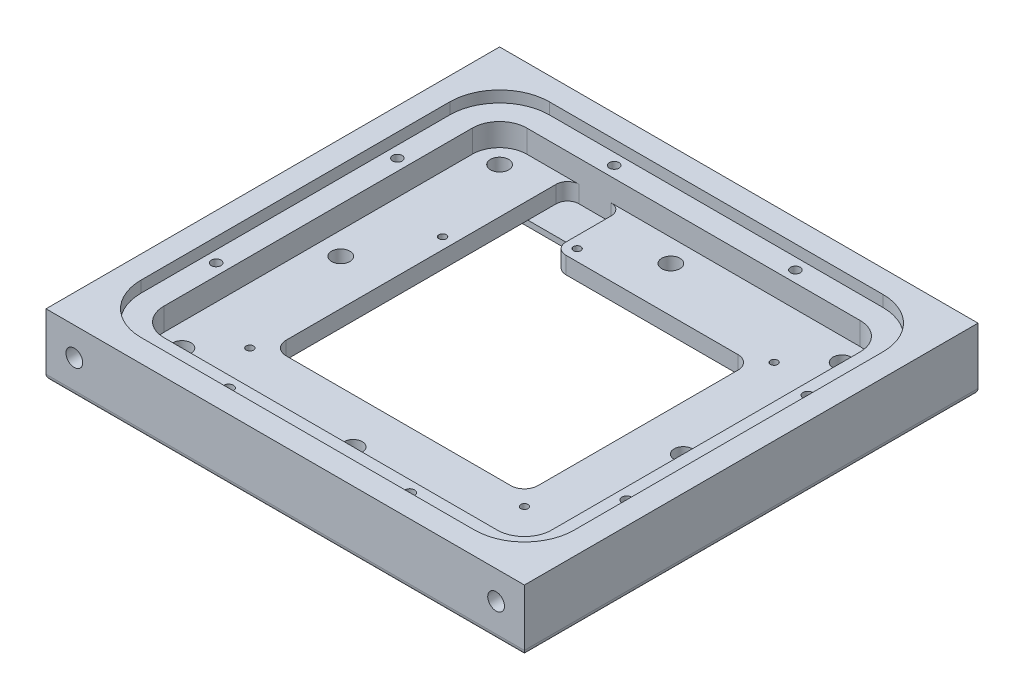
SolidWorks part; units mm, degrees
material "PE High Density"
ref_plane "Front Plane" through (0, 0, 0) normal (0, 0, 1) x (1, 0, 0)
ref_plane "Top Plane" through (0, 0, 0) normal (0, 1, 0) x (1, 0, 0)
ref_plane "Right Plane" through (0, 0, 0) normal (1, 0, 0) x (0, 0, -1)
sketch "Sketch2" plane through (0, 0, 0) normal (0, 1, 0) x (1, 0, 0)
  line L0 (-41.656, 22.1996) -> (-19.9136, 22.1996)
  line L1 (41.656, -38.1762) -> (-41.656, -38.1762)
  line L2 (41.656, -38.1762) -> (41.656, 38.1762)
  line L3 (41.656, 38.1762) -> (-41.656, 38.1762)
  line L4 (-41.656, -38.1762) -> (-41.656, 38.1762)
  line L5 (41.656, -38.1762) -> (-41.656, 38.1762) construction
  line L6 (41.656, 38.1762) -> (-41.656, -38.1762) construction
  line L7 (-19.9136, 22.1996) -> (-19.9136, 38.1762)
  line L8 (67.056, -63.5762) -> (-67.056, -63.5762)
  line L9 (-67.056, -63.5762) -> (-67.056, 63.5762)
  line L10 (67.056, 63.5762) -> (-67.056, 63.5762)
  line L11 (67.056, -63.5762) -> (67.056, 63.5762)
  point P0 (0, 0)
  point P13 (-38.481, -35.0012)
  point P14 (38.481, -35.0012)
  point P15 (38.481, 35.0012)
  point P16 (-16.7386, 35.0012)
  point P17 (-38.481, 19.0246)
  dimension "D1" = 83.312
  dimension "D2" = 76.3524
  dimension "D3" = 21.7424
  dimension "D4" = 15.9766
  dimension "D6" = 3.175
  dimension "D7" = 3.175
  dimension "D8" = 57.2008
  dimension "D9" = 80.137
  dimension "D10" = 24.9174
  dimension "D11" = 73.1774
  dimension "D5" = 25.4
extrude "Boss-Extrude1" add sketch "Sketch2" along normal blind 15.875 contours L8 L11 L10 L9 L1 L4 L3 L2 | L0 L7 L3 L4 region at (-30.7848, 0, -30.1879) region at (0, 0, 61.7281)
sketch "Sketch4" plane through (0, 0, 0) normal (0, 1, 0) x (1, 0, 0)
  line L0 (41.656, -38.1762) -> (41.656, 38.1762) construction
  line L1 (41.656, 38.1762) -> (-19.9136, 38.1762) construction
  line L2 (41.656, -38.1762) -> (-41.656, -38.1762) construction
  line L3 (-41.656, -38.1762) -> (-41.656, 22.1996) construction
  line L4 (-41.656, 22.1996) -> (-19.9136, 22.1996) construction
  line L5 (41.656, -38.1762) -> (41.656, 38.1762)
  line L6 (41.656, 38.1762) -> (-19.9136, 38.1762)
  line L7 (41.656, -38.1762) -> (-41.656, -38.1762)
  line L8 (-41.656, -38.1762) -> (-41.656, 22.1996)
  line L9 (-41.656, 22.1996) -> (-19.9136, 22.1996)
  line L10 (-19.9136, 22.1996) -> (-19.9136, 38.1762) construction
  line L11 (-19.9136, 22.1996) -> (-19.9136, 38.1762)
  line L12 (35.306, 31.8262) -> (-13.5636, 31.8262)
  line L13 (-13.5636, 15.8496) -> (-13.5636, 31.8262)
  line L14 (-35.306, 15.8496) -> (-13.5636, 15.8496)
  line L15 (-35.306, -31.8262) -> (-35.306, 15.8496)
  line L16 (35.306, -31.8262) -> (-35.306, -31.8262)
  line L17 (35.306, -31.8262) -> (35.306, 31.8262)
  dimension "D1" = 6.35
extrude "Boss-Extrude2" add sketch "Sketch4" along normal blind 9.525
sketch "Sketch5" plane through (0, 0, 0) normal (0, -1, 0) x (1, 0, 0)
  line L5 (46.736, -50.8762) -> (-46.736, -50.8762)
  line L6 (54.356, -43.2562) -> (54.356, 43.2562)
  line L7 (46.736, 50.8762) -> (-46.736, 50.8762)
  line L8 (-54.356, -43.2562) -> (-54.356, 43.2562)
  line L9 (54.356, -50.8762) -> (-54.356, 50.8762) construction
  line L10 (54.356, 50.8762) -> (-54.356, -50.8762) construction
  arc A0 (46.736, -50.8762) -> (54.356, -43.2562) centre (46.736, -43.2562) ccw
  arc A1 (-46.736, -50.8762) -> (-54.356, -43.2562) centre (-46.736, -43.2562) cw
  arc A2 (54.356, 43.2562) -> (46.736, 50.8762) centre (46.736, 43.2562) ccw
  arc A3 (-46.736, 50.8762) -> (-54.356, 43.2562) centre (-46.736, 43.2562) ccw
  point P0 (0, 0)
  dimension "D3" = 7.62
  dimension "D1" = 108.712
  dimension "D2" = 101.7524
extrude "Cut-Extrude2" cut sketch "Sketch5" against normal blind 3.175
hole_wizard "M2.5x0.45 Tapped Hole1" positions "Sketch6" profile "Sketch7" tap size "M2.5x0.45" standard "ANSI Metric"
sketch "Sketch6" plane through (0, 3.175, 0) normal (0, -1, 0) x (-1, 0, 0)
  point P0 (38.481, -35.0012)
  point P3 (-38.481, -35.0012)
  point P6 (38.481, 19.0246)
  point P9 (16.7386, 35.0012)
  point P12 (-38.481, 35.0012)
sketch "Sketch7" plane through (-38.481, 3.175, 35.0012) normal (1, 0, 0) x (0, 0, -1)
  line L0 (0, 0) -> (0, 6.9659)
  line L1 (0, 6.9659) -> (1.025, 6.35)
  line L2 (1.025, 6.35) -> (1.025, 0)
  line L5 (1.025, 0) -> (0, 0)
  line L10 (0, 6.9659) -> (-1.025, 6.35) construction
  line L11 (0, -6.35) -> (0, 107.95) construction
  dimension "Tap Drill Dia." = 2.05
  dimension "Tap Drill Depth" = 6.35
  dimension "Drill Angle" = 118
cosmetic thread "Hole Thread1" parameters "D1"=5.08, "D2"=2.5
cosmetic thread "Hole Thread2" parameters "D1"=5.08, "D2"=2.5
cosmetic thread "Hole Thread3" parameters "D1"=5.08, "D2"=2.5
cosmetic thread "Hole Thread4" parameters "D1"=5.08, "D2"=2.5
cosmetic thread "Hole Thread5" parameters "D1"=5.08, "D2"=2.5
hole_wizard "#10 Clearance Hole1" positions "Sketch8" profile "Sketch9" hole size "#10" standard "ANSI Inch" end condition through all
sketch "Sketch8" plane through (0, 3.175, 0) normal (0, -1, 0) x (-1, 0, 0)
  line L0 (54.356, -43.2562) -> (54.356, 43.2562) construction
  line L1 (-46.736, -50.8762) -> (46.736, -50.8762) construction
  line L2 (46.736, 50.8762) -> (-46.736, 50.8762) construction
  line L3 (-54.356, 43.2562) -> (-54.356, -43.2562) construction
  point P0 (48.006, -44.5262)
  point P2 (0, -44.5262)
  point P4 (-48.006, -44.5262)
  point P6 (-48.006, 0)
  point P8 (-48.006, 44.5262)
  point P10 (0, 44.5262)
  point P12 (48.006, 44.5262)
  point P14 (48.006, 0)
  dimension "D1" = 6.35
  dimension "D2" = 6.35
  dimension "D3" = 6.35
  dimension "D4" = 6.35
sketch "Sketch9" plane through (-48.006, 3.175, 44.5262) normal (1, 0, 0) x (0, 0, -1)
  line L0 (0, 0) -> (0, 12.7)
  line L1 (0, 12.7) -> (2.5527, 12.7)
  line L2 (2.5527, 12.7) -> (2.5527, 0)
  line L5 (2.5527, 0) -> (0, 0)
  line L11 (0, -6.35) -> (0, 107.95) construction
  dimension "Thru Hole Dia." = 5.1054
  dimension "Thru Hole Depth" = 12.7
sketch "Sketch10" plane through (0, 15.875, 0) normal (0, 1, 0) x (1, 0, 0)
  line L4 (54.356, -43.2562) -> (54.356, 43.2562)
  line L5 (-46.736, -50.8762) -> (46.736, -50.8762)
  line L6 (-54.356, 43.2562) -> (-54.356, -43.2562)
  line L7 (46.736, 50.8762) -> (-46.736, 50.8762)
  line L8 (54.356, -43.2562) -> (54.356, 43.2562)
  line L9 (-46.736, -50.8762) -> (46.736, -50.8762)
  line L10 (-54.356, 43.2562) -> (-54.356, -43.2562)
  line L11 (46.736, 50.8762) -> (-46.736, 50.8762)
  arc A4 (54.356, 43.2562) -> (46.736, 50.8762) centre (46.736, 43.2562) ccw
  arc A5 (46.736, -50.8762) -> (54.356, -43.2562) centre (46.736, -43.2562) ccw
  arc A6 (-54.356, -43.2562) -> (-46.736, -50.8762) centre (-46.736, -43.2562) ccw
  arc A7 (-46.736, 50.8762) -> (-54.356, 43.2562) centre (-46.736, 43.2562) ccw
  arc A8 (54.356, 43.2562) -> (46.736, 50.8762) centre (46.736, 43.2562) ccw
  arc A9 (46.736, -50.8762) -> (54.356, -43.2562) centre (46.736, -43.2562) ccw
  arc A10 (-54.356, -43.2562) -> (-46.736, -50.8762) centre (-46.736, -43.2562) ccw
  arc A11 (-46.736, 50.8762) -> (-54.356, 43.2562) centre (-46.736, 43.2562) ccw
  dimension "D1" = 0
extrude "Cut-Extrude3" cut sketch "Sketch10" against normal up to surface (6.35 mm away) up to face at (-38.481, 9.525, 33.9762)
sketch "Sketch11" plane through (0, 3.175, 0) normal (0, -1, 0) x (1, 0, 0)
  line L8 (43.2435, 39.7637) -> (-43.2435, 39.7637)
  line L9 (-43.2435, 39.7637) -> (-43.2435, -39.7637)
  line L10 (-43.2435, -39.7637) -> (43.2435, -39.7637)
  line L11 (43.2435, -39.7637) -> (43.2435, 39.7637)
  line L12 (40.0685, 39.7637) -> (-40.0685, 39.7637)
  line L13 (-43.2435, 36.5887) -> (-43.2435, -36.5887)
  line L14 (-40.0685, -39.7637) -> (40.0685, -39.7637)
  line L15 (43.2435, -36.5887) -> (43.2435, 36.5887)
  arc A0 (40.0685, -39.7637) -> (43.2435, -36.5887) centre (40.0685, -36.5887) ccw
  arc A1 (-43.2435, -36.5887) -> (-40.0685, -39.7637) centre (-40.0685, -36.5887) ccw
  arc A2 (40.0685, 39.7637) -> (43.2435, 36.5887) centre (40.0685, 36.5887) cw
  arc A3 (-40.0685, 39.7637) -> (-43.2435, 36.5887) centre (-40.0685, 36.5887) ccw
  dimension "D2" = 3.175
  dimension "D1" = 1.5875
extrude "Cut-Extrude4" cut sketch "Sketch11" against normal blind 1.6
sketch "Sketch12" plane through (0, 4.775, 0) normal (0, -1, 0) x (1, 0, 0)
  line L0 (-35.306, 31.8262) -> (-35.306, -15.8496) construction
  line L1 (35.306, 31.8262) -> (-35.306, 31.8262)
  line L2 (35.306, 31.8262) -> (35.306, -31.8262)
  line L3 (35.306, -31.8262) -> (-35.306, -31.8262)
  line L4 (-35.306, 31.8262) -> (-35.306, -31.8262)
  line L5 (-13.5636, -31.8262) -> (35.306, -31.8262) construction
extrude "Cut-Extrude5" cut sketch "Sketch12" against normal through all
fillet "Fillet1" radius 3.81 4 edges at (35.306, 7.15, -31.8262) (-35.306, 7.15, -31.8262) (35.306, 7.15, 31.8262) (-35.306, 7.15, 31.8262)
sketch "Sketch13" plane through (0, 0, 0) normal (0, -1, 0) x (1, 0, 0)
  line L4 (54.356, -43.2562) -> (54.356, 43.2562)
  line L5 (46.736, 50.8762) -> (-46.736, 50.8762)
  line L6 (-54.356, 43.2562) -> (-54.356, -43.2562)
  line L7 (-46.736, -50.8762) -> (46.736, -50.8762)
  line L8 (54.356, -43.2562) -> (54.356, 43.2562)
  line L9 (46.736, 50.8762) -> (-46.736, 50.8762)
  line L10 (-54.356, 43.2562) -> (-54.356, -43.2562)
  line L11 (-46.736, -50.8762) -> (46.736, -50.8762)
  line L12 (67.056, 63.5762) -> (-67.056, 63.5762)
  line L13 (-67.056, 63.5762) -> (-67.056, -63.5762)
  line L14 (-67.056, -63.5762) -> (67.056, -63.5762)
  line L15 (67.056, -63.5762) -> (67.056, 63.5762)
  line L16 (67.056, 63.5762) -> (-67.056, 63.5762)
  line L17 (-67.056, 63.5762) -> (-67.056, -63.5762)
  line L18 (-67.056, -63.5762) -> (67.056, -63.5762)
  line L19 (67.056, -63.5762) -> (67.056, 63.5762)
  arc A4 (46.736, -50.8762) -> (54.356, -43.2562) centre (46.736, -43.2562) ccw
  arc A5 (54.356, 43.2562) -> (46.736, 50.8762) centre (46.736, 43.2562) ccw
  arc A6 (-46.736, 50.8762) -> (-54.356, 43.2562) centre (-46.736, 43.2562) ccw
  arc A7 (-54.356, -43.2562) -> (-46.736, -50.8762) centre (-46.736, -43.2562) ccw
  arc A8 (46.736, -50.8762) -> (54.356, -43.2562) centre (46.736, -43.2562) ccw
  arc A9 (54.356, 43.2562) -> (46.736, 50.8762) centre (46.736, 43.2562) ccw
  arc A10 (-46.736, 50.8762) -> (-54.356, 43.2562) centre (-46.736, 43.2562) ccw
  arc A11 (-54.356, -43.2562) -> (-46.736, -50.8762) centre (-46.736, -43.2562) ccw
  dimension "D1" = 0
  dimension "D2" = 0
extrude "Cut-Extrude6" cut sketch "Sketch13" against normal blind 1.5875
fillet "Fillet2" radius 1.5875 4 edges at (67.056, 1.5875, 0) (0, 1.5875, 63.5762) (-67.056, 1.5875, 0) (0, 1.5875, -63.5762)
sketch "Sketch14" plane through (0, 9.525, 0) normal (0, 1, 0) x (1, 0, 0)
  line L1 (-35.306, 28.0162) -> (-19.9136, 28.0162)
  line L2 (-35.306, 28.0162) -> (-35.306, 50.8762)
  line L3 (-35.306, 50.8762) -> (-19.9136, 50.8762)
  line L4 (-19.9136, 28.0162) -> (-19.9136, 50.8762)
  line L6 (46.736, 50.8762) -> (-46.736, 50.8762) construction
  circle A0 centre (-16.7386, 35.0012) radius 1.025 construction
  dimension "D1" = 3.175
extrude "Cut-Extrude7" cut sketch "Sketch14" against normal up to surface (4.75 mm away) up to face at (0, 4.775, 0)
fillet "Fillet3" radius 3.175 3 edges at (-19.9136, 7.15, -50.8762) (-35.306, 7.15, -50.8762) (-19.9136, 7.15, -31.8262)
sketch "Sketch15" plane through (0, 15.875, 0) normal (0, 1, 0) x (1, 0, 0)
  line L0 (54.356, -43.2562) -> (54.356, 43.2562) construction
  line L1 (-46.736, -50.8762) -> (46.736, -50.8762) construction
  line L2 (-54.356, 43.2562) -> (-54.356, -43.2562) construction
  line L3 (46.736, 50.8762) -> (-46.736, 50.8762) construction
  line L4 (54.356, -43.2562) -> (54.356, 43.2562)
  line L5 (-46.736, -50.8762) -> (46.736, -50.8762)
  line L6 (-54.356, 43.2562) -> (-54.356, -43.2562)
  line L7 (46.736, 50.8762) -> (-46.736, 50.8762)
  line L8 (60.706, -43.2562) -> (60.706, 43.2562)
  line L9 (46.736, 57.2262) -> (-46.736, 57.2262)
  line L10 (-60.706, 43.2562) -> (-60.706, -43.2562)
  line L11 (-46.736, -57.2262) -> (46.736, -57.2262)
  line L16 (-67.056, -63.5762) -> (67.056, -63.5762)
  line L17 (67.056, -63.5762) -> (67.056, 63.5762)
  line L18 (67.056, 63.5762) -> (-67.056, 63.5762)
  line L19 (-67.056, 63.5762) -> (-67.056, -63.5762)
  line L20 (-67.056, -63.5762) -> (67.056, -63.5762)
  line L21 (67.056, -63.5762) -> (67.056, 63.5762)
  line L22 (67.056, 63.5762) -> (-67.056, 63.5762)
  line L23 (-67.056, 63.5762) -> (-67.056, -63.5762)
  arc A0 (46.736, -50.8762) -> (54.356, -43.2562) centre (46.736, -43.2562) ccw construction
  arc A1 (-54.356, -43.2562) -> (-46.736, -50.8762) centre (-46.736, -43.2562) ccw construction
  arc A2 (54.356, 43.2562) -> (46.736, 50.8762) centre (46.736, 43.2562) ccw construction
  arc A3 (-46.736, 50.8762) -> (-54.356, 43.2562) centre (-46.736, 43.2562) ccw construction
  arc A4 (46.736, -50.8762) -> (54.356, -43.2562) centre (46.736, -43.2562) ccw
  arc A5 (-54.356, -43.2562) -> (-46.736, -50.8762) centre (-46.736, -43.2562) ccw
  arc A6 (54.356, 43.2562) -> (46.736, 50.8762) centre (46.736, 43.2562) ccw
  arc A7 (-46.736, 50.8762) -> (-54.356, 43.2562) centre (-46.736, 43.2562) ccw
  arc A8 (60.706, 43.2562) -> (46.736, 57.2262) centre (46.736, 43.2562) ccw
  arc A9 (-46.736, 57.2262) -> (-60.706, 43.2562) centre (-46.736, 43.2562) ccw
  arc A10 (-60.706, -43.2562) -> (-46.736, -57.2262) centre (-46.736, -43.2562) ccw
  arc A11 (46.736, -57.2262) -> (60.706, -43.2562) centre (46.736, -43.2562) ccw
  line M29 (-67.056, -63.5762) -> (67.056, -63.5762)
  line M30 (67.056, -63.5762) -> (67.056, 63.5762)
  line M31 (67.056, 63.5762) -> (-67.056, 63.5762)
  line M32 (-67.056, 63.5762) -> (-67.056, -63.5762)
  dimension "D1" = 6.35
  dimension "D2" = 0
extrude "Boss-Extrude3" add sketch "Sketch15" along normal blind 3.175 contours A11 L11 A10 L10 A9 L9 A8 L8 M32 M29 M30 M31 region at (-65.2079, 15.875, 0)
hole_wizard "#6-32 Tapped Hole1" positions "Sketch16" profile "Sketch18" tap size "#6-32" standard "ANSI Inch"
sketch "Sketch16" plane through (0, 15.875, 0) normal (0, 1, 0) x (1, 0, 0)
  line L28 (57.531, -43.2562) -> (57.531, 43.2562)
  line L29 (-46.736, -54.0512) -> (46.736, -54.0512)
  line L30 (-57.531, 43.2562) -> (-57.531, -43.2562)
  line L31 (46.736, 54.0512) -> (-46.736, 54.0512)
  line L32 (57.531, -43.2562) -> (57.531, 43.2562) construction
  line L33 (-46.736, -54.0512) -> (46.736, -54.0512) construction
  line L34 (-57.531, 43.2562) -> (-57.531, -43.2562) construction
  line L35 (46.736, 54.0512) -> (-46.736, 54.0512) construction
  arc A24 (57.531, 43.2562) -> (46.736, 54.0512) centre (46.736, 43.2562) ccw
  arc A25 (46.736, -54.0512) -> (57.531, -43.2562) centre (46.736, -43.2562) ccw
  arc A26 (-57.531, -43.2562) -> (-46.736, -54.0512) centre (-46.736, -43.2562) ccw
  arc A27 (-46.736, 54.0512) -> (-57.531, 43.2562) centre (-46.736, 43.2562) ccw
  arc A28 (57.531, 43.2562) -> (46.736, 54.0512) centre (46.736, 43.2562) ccw construction
  arc A29 (46.736, -54.0512) -> (57.531, -43.2562) centre (46.736, -43.2562) ccw construction
  arc A30 (-57.531, -43.2562) -> (-46.736, -54.0512) centre (-46.736, -43.2562) ccw construction
  arc A31 (-46.736, 54.0512) -> (-57.531, 43.2562) centre (-46.736, 43.2562) ccw construction
  point P141 (-25.4, 54.0512)
  point P143 (-57.531, 25.4)
  point P145 (-57.531, -25.4)
  point P147 (-25.4, -54.0512)
  dimension "D2" = 25.4
  dimension "D3" = 25.4
  dimension "D4" = 25.4
  dimension "D1" = 3.175
cosmetic thread "Hole Thread6" parameters "D1"=14.224, "D2"=3.5052
cosmetic thread "Hole Thread7" parameters "D1"=14.224, "D2"=3.5052
cosmetic thread "Hole Thread8" parameters "D1"=14.224, "D2"=3.5052
cosmetic thread "Hole Thread9" parameters "D1"=14.224, "D2"=3.5052
sketch "Sketch18" plane through (-25.4, 15.875, 54.0512) normal (1, 0, 0) x (0, 0, 1)
  line L0 (0, 0) -> (0, 10.3377)
  line L1 (0, 10.3377) -> (1.3525, 9.525)
  line L2 (1.3525, 9.525) -> (1.3525, 0)
  line L5 (1.3525, 0) -> (0, 0)
  line L10 (0, 10.3377) -> (-1.3526, 9.525) construction
  line L11 (0, -6.35) -> (0, 107.95) construction
  dimension "Tap Drill Dia." = 2.7051
  dimension "Tap Drill Depth" = 9.525
  dimension "Drill Angle" = 118
mirror "Mirror1" about plane through (0, 0, 0) normal (1, 0, 0) of "#6-32 Tapped Hole1"
cosmetic thread "Hole Thread10" parameters "D1"=14.224, "D2"=3.5052
cosmetic thread "Hole Thread11" parameters "D1"=14.224, "D2"=3.5052
cosmetic thread "Hole Thread12" parameters "D1"=14.224, "D2"=3.5052
cosmetic thread "Hole Thread13" parameters "D1"=14.224, "D2"=3.5052
sketch "Sketch19" plane through (0, 0, -63.5762) normal (0, 0, -1) x (-1, 0, 0)
  line L0 (-67.056, 11.1125) -> (-59.1185, 11.1125) construction
  line L1 (-67.056, 19.05) -> (-67.056, 3.175) construction
  line L2 (-59.1185, 11.1125) -> (-59.1185, 19.05) construction
  line L3 (-67.056, 19.05) -> (67.056, 19.05) construction
  line L5 (67.056, 19.05) -> (67.056, 3.175) construction
  line L6 (67.056, 11.1125) -> (59.1185, 11.1125) construction
  circle A0 centre (-59.1185, 11.1125) radius 2.3495
  circle A1 centre (59.1185, 11.1125) radius 2.3495
  dimension "D1" = 4.699
extrude "Cut-Extrude8" cut sketch "Sketch19" against normal blind 6.35
extrude "Cut-Extrude9" cut sketch "Sketch19<2>" along normal blind 6.35 from surface starting at face at (0, 11.1125, 63.5762)
sketch "Sketch19<2>" plane through (0, 0, -63.5762) normal (0, 0, -1) x (-1, 0, 0) same geometry as "Sketch19"
equation "\"D3@Sketch16\"=\"D2@Sketch16\""
equation "\"D4@Sketch16\"=\"D2@Sketch16\""
